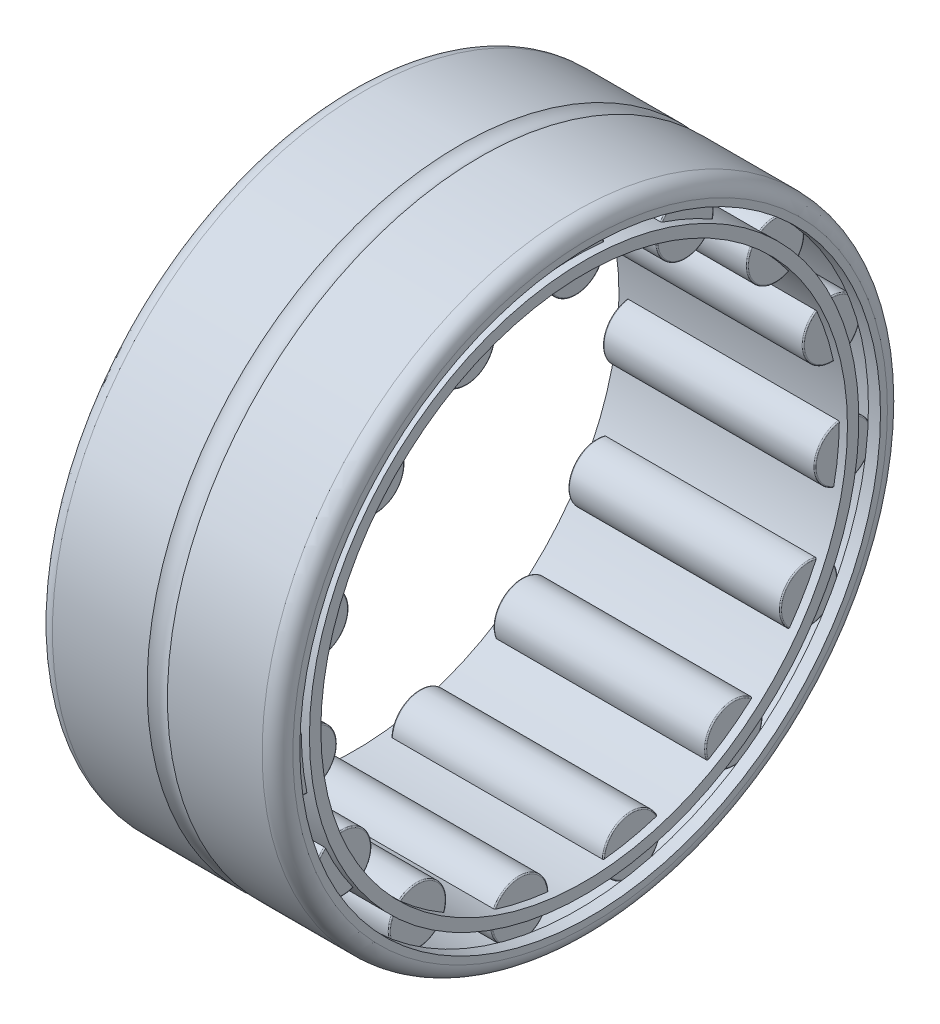
SolidWorks part; units mm, degrees
ref_plane "Plane1" through (0, 0, 0) normal (0, 0, 1) x (1, 0, 0)
ref_plane "Plane2" through (0, 0, 0) normal (0, 1, 0) x (1, 0, 0)
ref_plane "Plane3" through (0, 0, 0) normal (1, 0, 0) x (0, 0, -1)
sketch "Clipboard" plane through (0, 0, 0) normal (0, 0, 1) x (1, 0, 0)
  line L0 (-10, 0) -> (10, 0) construction
  line L1 (41.1529, 1.4371) -> (62.7517, -4.3503)
  line L2 (41.1529, 1.4371) -> (75.4583, 10.6292)
  line L3 (41.1529, 1.4371) -> (62.7517, -4.3503)
  line L4 (41.1529, 1.4371) -> (-22.3471, -0.7804)
  dimension "BallCLRad" = 35.5155
  dimension "Bore" = 63.5
sketch "InnRacSke" plane through (0, 0, 0) normal (0, 0, 1) x (1, 0, 0)
  line L0 (-14.2875, 38.3286) -> (-15.875, 38.3286)
  line L1 (-15.875, 38.3286) -> (-15.875, 39.243)
  line L2 (-13.843, 41.275) -> (-1.344, 41.275)
  line L3 (1.344, 41.275) -> (13.843, 41.275)
  line L4 (15.875, 39.243) -> (15.875, 38.3286)
  line L5 (15.875, 38.3286) -> (14.2875, 38.3286)
  line L6 (14.2875, 38.3286) -> (14.2875, 39.2811)
  line L7 (14.2875, 39.2811) -> (-14.2875, 39.2811)
  line L8 (-14.2875, 39.2811) -> (-14.2875, 38.3286)
  line L9 (-31.75, 0) -> (31.75, 0) construction
  arc A0 (-15.875, 39.243) -> (-13.843, 41.275) centre (-13.843, 39.243) cw
  arc A1 (-1.344, 41.275) -> (1.344, 41.275) centre (0, 42.799) ccw
  arc A2 (13.843, 41.275) -> (15.875, 39.243) centre (13.843, 39.243) cw
  dimension "D1" = 78.5622
revolve "Race" add sketch "InnRacSke" angle 360 about L9 reverse direction yes
sketch "RolDetSke" plane through (0, 0, 0) normal (0, 0, 1) x (1, 0, 0)
  line L0 (-14.0018, 39.131) -> (-14.0017, 35.5155)
  line L1 (-14.0017, 35.5155) -> (14.0017, 35.5155)
  line L2 (14.0017, 35.5155) -> (14.0018, 39.131)
  line L3 (13.8511, 39.2816) -> (-13.8511, 39.2816)
  line L4 (-28.575, 35.5155) -> (28.575, 35.5155) construction
  arc A0 (14.0018, 39.131) -> (13.8511, 39.2816) centre (13.8511, 39.131) ccw
  arc A1 (-13.8511, 39.2816) -> (-14.0018, 39.131) centre (-13.8511, 39.131) ccw
  dimension "Roller_length" = 28.0035
  dimension "Roller_diameter" = 7.5321
revolve "RollerDetailed" add sketch "RolDetSke" angle 360 about L4 reverse direction yes
ref_axis "Axis1" through (-50, 0, 0) along (1, 0, 0)
sketch "CagSpiSke" plane through (0, 0, 0) normal (0, 0, 1) x (1, 0, 0)
  line L0 (15.0812, 34.7623) -> (15.0812, 36.2688)
  line L1 (15.0812, 36.2688) -> (-15.0813, 36.2688)
  line L2 (-15.0813, 36.2688) -> (-15.0813, 34.7623)
  line L3 (-15.0813, 34.7623) -> (15.0812, 34.7623)
  line L4 (-31.75, 0) -> (31.75, 0) construction
  dimension "D2" = 69.5247
  dimension "halfWidth" = 15.0813
revolve "CageSpine" add sketch "CagSpiSke" angle 360 about L4
pattern_circular "RollersDetailed" count 15 every 24 about axis through (-50, 0, 0) along (1, 0, 0) of "RollerDetailed"
sketch "RolSimSke" plane through (0, 0, 0) normal (0, 0, 1) x (1, 0, 0)
  line L0 (-25.4, 0) -> (25.4, 0) construction
  line L2 (-13.8511, 39.2821) -> (13.8511, 39.2821)
  line L3 (-14.0018, 39.1315) -> (-14.0018, 31.9006)
  line L4 (-13.8511, 31.75) -> (13.8511, 31.75)
  line L5 (14.0017, 39.1315) -> (14.0017, 31.9006)
  arc A0 (-14.0018, 31.9006) -> (-13.8511, 31.75) centre (-13.8511, 31.9006) ccw
  arc A1 (-13.8511, 39.2821) -> (-14.0018, 39.1315) centre (-13.8511, 39.1315) ccw
  arc A2 (14.0017, 39.1315) -> (13.8511, 39.2821) centre (13.8511, 39.1315) ccw
  arc A3 (13.8511, 31.75) -> (14.0017, 31.9006) centre (13.8511, 31.9006) ccw
  point P10 (-14.0018, 31.75)
  point P15 (14.0017, 39.2821)
  point P18 (14.0017, 31.75)
  dimension "Bore" = 63.5
  dimension "D1" = 0.1506
  dimension "Roller_length" = 28.0035
  dimension "Roller_diameter" = 7.5321
  dimension "halfWidth" = 14.0017
revolve "RollersSimplified" [suppressed] add sketch "RolSimSke" angle 360 about L0
equation "\"BallCLRad@Clipboard\" =  ( \"D1@InnRacSke\" + \"Bore@Clipboard\" )  / 4"
equation "\"RollerCLRad@RolDetSke\" = \"BallCLRad@Clipboard\""
equation "\"offset@InnRacSke\" = \"radius@InnRacSke\" * .75"
equation "\"halfCyl@InnRacSke\" = \"Cyl_Len@InnRacSke\" / 2"
equation "\"Roller_diameter@RolDetSke\" =  ( \"D1@InnRacSke\" - \"Bore@Clipboard\" )  / 2 + .001"
equation "\"Roller_radius@RolDetSke\" = \"Roller_diameter@RolDetSke\" / 50"
equation "\"Roller_length@RolDetSke\" = \"Cyl_Len@InnRacSke\" * .98"
equation "\"halfLength@RolDetSke\" = \"Roller_length@RolDetSke\" / 2"
equation "\"Cage_width@CagSpiSke\" =  ( \"Cyl_Len@InnRacSke\" + \"Width@InnRacSke\" )  / 2"
equation "\"halfWidth@CagSpiSke\" = \"Cage_width@CagSpiSke\" / 2"
equation "\"Cage_thickness@CagSpiSke\"  = \"Roller_diameter@RolDetSke\" / 5"
equation "\"D2@CagSpiSke\" =  \"RollerCLRad@RolDetSke\" * 2 - \"Cage_thickness@CagSpiSke\""
equation "\"Roller_length@RolSimSke\" = \"Cyl_Len@InnRacSke\" * .98"
equation "\"halfWidth@RolSimSke\" = \"Roller_length@RolSimSke\" / 2"
equation "\"D1@RolSimSke\" = \"Roller_radius@RolDetSke\""
equation "\"Roller_diameter@RolSimSke\" =  ( \"D1@InnRacSke\" - \"Bore@Clipboard\" )  / 2 + .001"
equation "\"Max_count@Clipboard\" = int( 3.14159265 / atn(( \"Roller_diameter@RolDetSke\" / 2) / sqr( \"RollerCLRad@RolDetSke\"  *  \"RollerCLRad@RolDetSke\" - ( \"Roller_diameter@RolDetSke\" / 2) *  ( \"Roller_diameter@RolDetSke\" / 2))))"
equation "\"Max_count@Clipboard\" = ((sgn( \"Max_count@Clipboard\" - \"Count@Clipboard\" )-1)*( \"Max_count@Clipboard\" - \"Count@Clipboard\" ))/-2+ \"Count@Clipboard\""
equation "\"Count@RollersDetailed\" = int( \"Show_count@Clipboard\" ) "
equation "\"Count@RollersDetailed\" = ((sgn( \"Count@RollersDetailed\" - \"Max_count@Clipboard\" )-1)*( \"Count@RollersDetailed\" - \"Max_count@Clipboard\" ))/-2+ \"Max_count@Clipboard\""
equation "\"Count@RollersDetailed\" = ((sgn( \"Count@RollersDetailed\" - \"Min_count@Clipboard\" )+1)*( \"Count@RollersDetailed\" - \"Min_count@Clipboard\"))/2 +\"Min_count@Clipboard\""
equation "\"Angle@RollersDetailed\" = 360.0 / \"Max_count@Clipboard\""
equation "\"Angle@CageSpine\" =  \"Angle@RollersDetailed\" * ( \"Count@RollersDetailed\" -1 + int( \"Count@RollersDetailed\" / \"Max_count@Clipboard\" ) )  + 0.001 -  int( \"Count@RollersDetailed\" / \"Max_count@Clipboard\" ) * 0.001"
equation "\"Angle@CageSpine\" =  \"Angle@CageSpine\" * int( \"Min_count@Clipboard\" / 2) + int(1 / \"Min_count@Clipboard\")  * 0.001"
equation "\"Bore@RolSimSke\" = \"Bore@Clipboard\""
